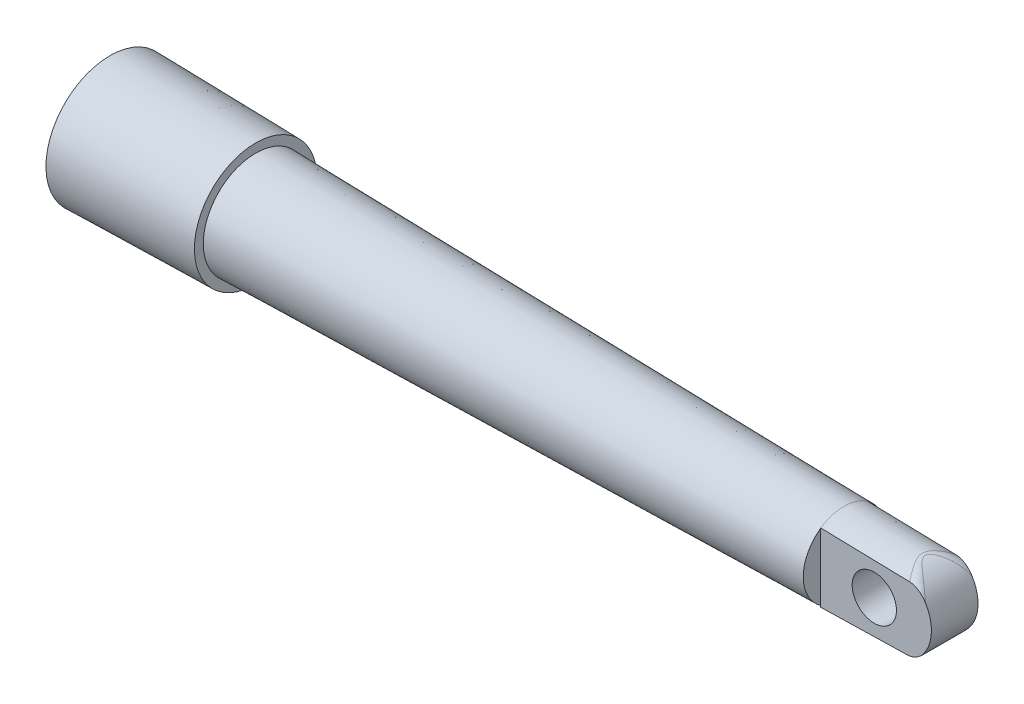
SolidWorks part; units mm, degrees
ref_plane "Front Plane" through (0, 0, 0) normal (0, 0, 1) x (1, 0, 0)
ref_plane "Top Plane" through (0, 0, 0) normal (0, 1, 0) x (1, 0, 0)
ref_plane "Right Plane" through (0, 0, 0) normal (1, 0, 0) x (0, 0, -1)
sketch "Sketch1" plane through (0, 0, 0) normal (0, 0, 1) x (1, 0, 0)
  line L0 (31.5, 0) -> (0, 0)
  line L1 (0, 0) -> (0, 2.75)
  line L2 (0, 2.75) -> (6.25, 2.63)
  line L3 (6.25, 2.63) -> (6.25, 2.25)
  line L6 (31.5, 0) -> (31.5, 1.75)
  line L7 (31.5, 1.75) -> (6.25, 2.25)
  dimension "D1" = 2.75
  dimension "D2" = 2.63
  dimension "D3" = 2.25
  dimension "D4" = 1.75
  dimension "D5" = 31.5
  dimension "D6" = 6.25
revolve "Revolve1" add sketch "Sketch1" angle 360 about L0
sketch "Sketch2" plane through (0, 0, 0) normal (0, 0, 1) x (1, 0, 0)
  line L0 (31.5, 0) -> (36.25, 0) construction
  line L1 (31.5, -1.75) -> (31.5, 1.75) construction
  line L2 (31.5, 1.75) -> (34.9141, 1.6824)
  line L3 (31.5, -1.75) -> (34.9141, -1.6824)
  line L4 (31.5, 1.75) -> (6.25, 2.25) construction
  line L5 (31.5, 1.75) -> (31.5, -1.75)
  arc A0 (34.9141, 1.6824) -> (34.9141, -1.6824) centre (34.5227, 0) cw
  dimension "D1" = 4.75
extrude "Boss-Extrude1" add sketch "Sketch2" along normal mid plane 2
sketch "Sketch3" plane through (0, 0, 0) normal (0, 0, 1) x (1, 0, 0)
  line L0 (31.5, 1.75) -> (31.5, 2.4684)
  line L1 (31.5, 2.4684) -> (36.6527, 2.4684)
  line L2 (36.6527, 2.4684) -> (36.6527, 1.648)
  line L3 (36.6527, 1.648) -> (31.5, 1.75)
  line L4 (34.9141, 1.6824) -> (31.5, 1.75) construction
  line L5 (31.5, -1.4361) -> (31.5, 1.4361) construction
  line L6 (31.5, -0.0316) -> (36.909, -0.0316) construction
  line L7 (31.5, 1.4361) -> (31.5, -1.4361) construction
  point P7 (31.5, 0)
  dimension "D1" = 2.5
revolve "Cut-Revolve1" cut sketch "Sketch3" angle 360 about L6
sketch "Sketch4" plane through (0, 0, 1) normal (0, 0, 1) x (1, 0, 0)
  line L0 (31.5, 0) -> (34.5227, 0) construction
  line L1 (31.5, -1.4361) -> (31.5, 1.4361) construction
  circle A0 centre (33.7992, 0) radius 0.95
  arc A1 (35.5223, -1.4087) -> (35.6084, 1.3435) centre (34.5227, 0) ccw construction
  point P7 (34.7492, 0)
  point P8 (36.2492, -0.054)
  dimension "D1" = 1.9
  dimension "D2" = 1.5
extrude "Cut-Extrude1" cut sketch "Sketch4" against normal through all
fillet "Fillet1" radius 0.5 4 edges at (34.9141, -1.6824, 0) (34.9199, 1.681, 0.0652)
sketch "Sketch5" plane through (0, 0, 0) normal (-1, 0, 0) x (0, 0, 1)
  circle A0 centre (0, 0) radius 1
  dimension "D1" = 2
extrude "Cut-Extrude2" cut sketch "Sketch5" against normal blind 26.5
